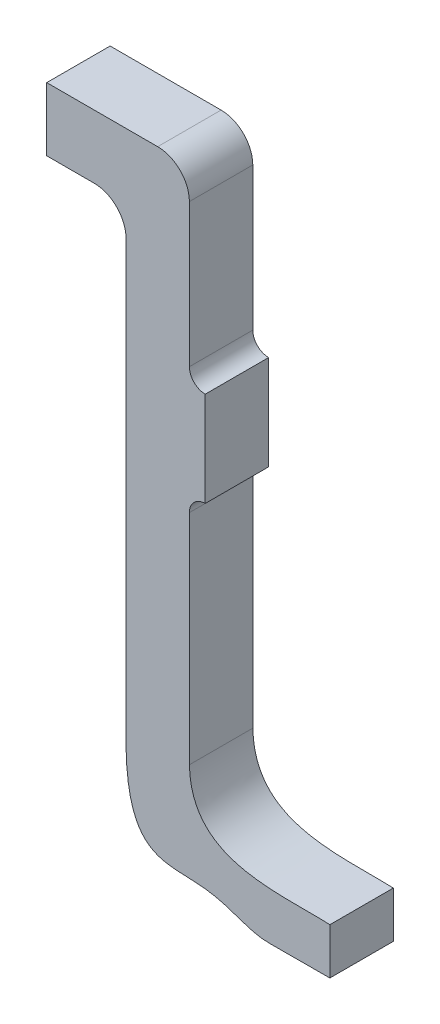
SolidWorks part; units mm, degrees
ref_plane "Front Plane" through (0, 0, 0) normal (0, 0, 1) x (1, 0, 0)
ref_plane "Top Plane" through (0, 0, 0) normal (0, 1, 0) x (1, 0, 0)
ref_plane "Right Plane" through (0, 0, 0) normal (1, 0, 0) x (0, 0, -1)
sketch "Sketch1" plane through (0, 0, 0) normal (0, 0, 1) x (1, 0, 0)
  line L0 (-0.05, 1.7994) -> (-0.05, 1.9994) construction
  line L1 (-0.05, 1.9994) -> (0.4, 1.9994) construction
  line L2 (3.2831, 1.9994) -> (3.2831, 0) construction
  line L3 (3.2831, 0) -> (0, 0) construction
  line L4 (-0.05, 1.9994) -> (-0.05, 1.7994)
  line L5 (-0.05, 1.9994) -> (0.3, 1.9994)
  line L6 (0.8431, 0.1457) -> (0.8431, 0)
  line L7 (-0.05, 1.9994) -> (0.4, 1.9994)
  line L8 (0.4, 1.8994) -> (0.4, 0.9485)
  line L9 (0.4, 0.9485) -> (0.4, 0.3609)
  line L10 (0.2, 0.6994) -> (0.2, 0.314)
  line L12 (0.8431, 0.1457) -> (0.8431, 0)
  line L15 (0.2, 0.6994) -> (0.2, 1.6994)
  line L16 (0.1, 1.7994) -> (-0.05, 1.7994)
  line L17 (0.75, 1.9994) -> (3.2831, 1.9994) construction
  arc A2 (0.1, 1.7994) -> (0.2, 1.6994) centre (0.1, 1.6994) cw
  arc A3 (0.4, 1.8994) -> (0.3, 1.9994) centre (0.3, 1.8994) ccw
  spline S0 degree 3 poles (0.4, 0.3609) (0.4053, 0.1106) (0.6784, 0.1534) (0.8431, 0.1457) knots 0 0 0 0 1 1 1 1
  spline S1 degree 3 poles (0.2, 0.314) (0.2051, 0.0172) (0.3361, 0.0651) (0.5245, 0.0361) (0.5973, -0.0003) (0.7274, -0.0011) (0.7369, 0.0003) (0.8431, 0) knots 0 0 0 0 0.386745 0.431585 0.602654 0.661634 1 1 1 1
  point P12 (0.4, 0.0611)
  point P18 (0.2311, 0.0641)
  point P26 (0.4241, 0.025)
  point P28 (0.25, 0.0821)
  point P29 (0.6073, 0.028)
  point P30 (0.4478, 0.019)
  point P31 (0.8451, 0)
  point P32 (0.6374, 0)
  point P33 (0.4719, 0.0581)
  point P34 (0, 0)
  point P35 (0.4649, 0.045)
  point P36 (0.2662, 0.0829)
  point P37 (0.4778, 0.2184)
  point P38 (0.6233, 0.1787)
  point P39 (0.4828, 0.2019)
  point P40 (0.7043, 0.1705)
  point P41 (0.8431, 0.1457)
  point P42 (0.7076, 0.1473)
  point P43 (0.4811, 0.1953)
  dimension "D4" = 0.15
  dimension "D5" = 1
  dimension "D6" = 0.1
  dimension "D1" = 2
  dimension "D2" = 0.8
  dimension "D3" = 0.2
  dimension "D7" = 0.9509
extrude "Boss-Extrude1" add sketch "Sketch1" along normal blind 0.2 contours L10 S1 L6 S0 L9 L8 A3 L5 L4 L16 A2 L15 region at (0.3204, 0.9968, 0)
sketch "Sketch2" plane through (0.4, 0, 0) normal (1, 0, 0) x (0, 0, -1)
  line L0 (-0.2, 1.8994) -> (-0.2, 0.3609) construction
  line L1 (-0.2, 1.3983) -> (0, 1.3983)
  line L2 (-0.2, 1.3983) -> (-0.2, 1.0997)
  line L3 (-0.2, 1.0997) -> (0, 1.0997)
  line L4 (0, 1.3983) -> (0, 1.0997)
  line L5 (0, 1.8994) -> (0, 0.3609) construction
extrude "Boss-Extrude2" add sketch "Sketch2" along normal blind 0.05
fillet "Fillet1" radius 0.05 2 edges at (0.4, 1.0997, 0.1) (0.4, 1.3983, 0.1)
